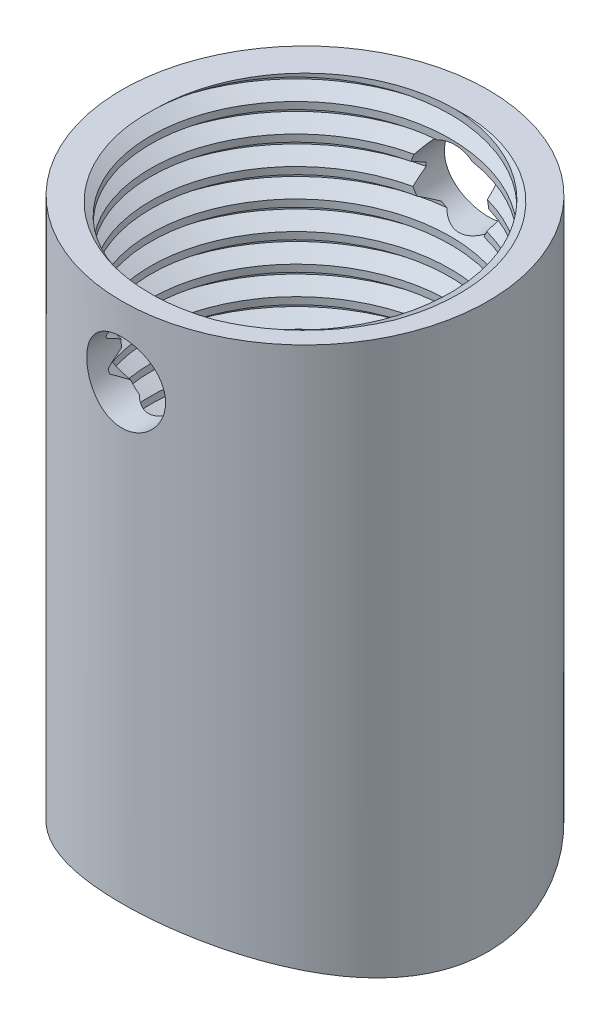
SolidWorks part; units mm, degrees
ref_plane "Front Plane" through (0, 0, 0) normal (0, 0, 1) x (1, 0, 0)
ref_plane "Top Plane" through (0, 0, 0) normal (0, 1, 0) x (1, 0, 0)
ref_plane "Right Plane" through (0, 0, 0) normal (1, 0, 0) x (0, 0, -1)
sketch "Sketch1" plane through (0, 0, 0) normal (0, 1, 0) x (1, 0, 0)
  circle A0 centre (0, 0) radius 13.335
  circle A1 centre (0, 0) radius 16.51
  dimension "D1" = 26.67
  dimension "D2" = 3.175
extrude "Boss-Extrude1" add sketch "Sketch1" along normal blind 50.8
sketch "Sketch2" plane through (0, 0, 0) normal (0, 1, 0) x (1, 0, 0)
  circle A0 centre (0, 0) radius 13.335 construction
  circle A1 centre (0, 0) radius 13.335
extrude "Boss-Extrude2" add sketch "Sketch2" along normal blind 12.7
sketch "Sketch3" plane through (0, 0, 0) normal (0, 0, 1) x (1, 0, 0)
  line L0 (-16.51, 0) -> (16.51, 0) construction
  line L5 (-16.51, 50.8) -> (-16.51, 0) construction
  line L7 (-16.51, 0) -> (16.51, 0)
  arc A0 (-16.51, 0) -> (16.51, 0) centre (0, -34.337) cw
  point P6 (0, 3.763)
  dimension "D2" = 38.1
extrude "Cut-Extrude2" cut sketch "Sketch3" against normal through all and the other way through all
other "Move Face1" flip direction yes face at (0, 12.7, 13.335) offset 0.1778 parameters "D1"=0.1778
thread "Thread1" pitch 2.54 method cut profile "Thread Profile1" start angle 0, offset 2.54, length 0, pitch 2.54, diameter 27.0256
ref_plane "Plane1" through (-13.5128, 53.34, 0) normal (0, 0, 1) x (-1, 0, 0)
sketch "Thread Profile1" plane through (-13.5128, 53.34, 0) normal (0, 0, 1) x (-1, 0, 0)
  line L0 (0, 0) -> (0, 2.54) construction
  line L1 (0, 0) -> (1.3748, 0.7937)
  line L2 (1.3748, 0.7937) -> (1.3748, 1.1112)
  line L3 (1.3748, 1.1112) -> (0, 1.905)
  line L4 (1.3748, 0.9525) -> (0, 0.9525) construction
  line L11 (0, 0) -> (0, 1.905)
  point P2 (0, 0)
  dimension "Pitch" = 2.54
  dimension "Profile_Angle" = 60
  dimension "Profile_Land" = 0.3175
  dimension "Profile_Height" = 1.3748
sketch "Sketch4" plane through (0, 0, 0) normal (0, 0, 1) x (1, 0, 0)
  line L0 (0, 50.8) -> (0, 3.763) construction
  circle A0 centre (0, 44.45) radius 3.556
  dimension "D1" = 7.112
  dimension "D2" = 44.45
extrude "Cut-Extrude3" cut sketch "Sketch4" against normal through all and the other way through all
